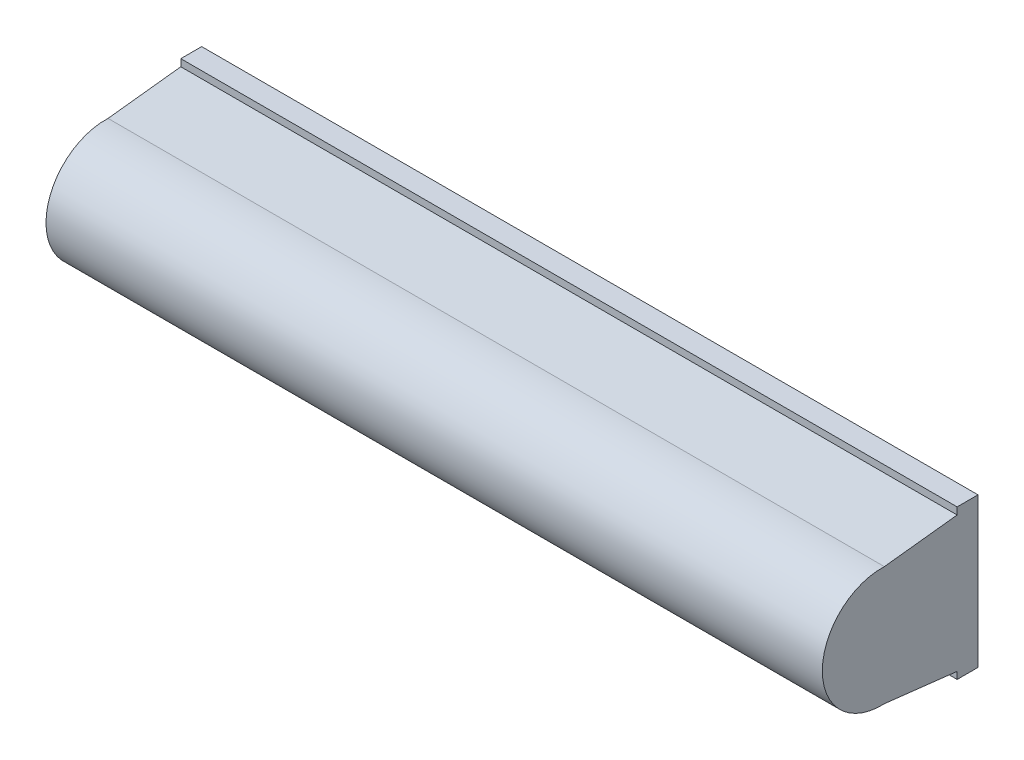
SolidWorks part; units mm, degrees
ref_plane "xy_plane" through (0, 0, 0) normal (0, 0, 1) x (1, 0, 0)
ref_plane "zx_plane" through (0, 0, 0) normal (0, 1, 0) x (1, 0, 0)
ref_plane "yz_plane" through (0, 0, 0) normal (1, 0, 0) x (0, 0, -1)
ref_axis "x_axis" through (-80.9, 0, 0) along (1, 0, 0)
ref_axis "y_axis" through (0, -50, 0) along (0, 1, 0)
ref_axis "z_axis" through (0, 0, -80.9) along (0, 0, 1)
sketch "Sketch1" plane through (0, 0, 0) normal (1, 0, 0) x (0, 0, -1)
  line L0 (0, -15.405) -> (0, 15.405)
  line L1 (0, 15.405) -> (-4.3, 15.405)
  line L2 (-4.3, 15.405) -> (-4.3, 13.955)
  line L3 (-4.3, 13.955) -> (-19.2957, 12.2383)
  line L4 (-19.2957, -12.2383) -> (-4.3, -13.955)
  line L5 (-4.3, -13.955) -> (-4.3, -15.405)
  line L6 (-4.3, -15.405) -> (0, -15.405)
  line L7 (80.9, 0) -> (-80.9, 0) construction
  line L8 (0, 50) -> (0, -50) construction
  line L9 (0, -50) -> (0, 50) construction
  arc A0 (-19.2957, 12.2383) -> (-19.2957, -12.2383) centre (-19.83, 0) ccw
  dimension "D1" = 12.25
  dimension "D2" = 32.08
  dimension "D3" = 4.3
  dimension "D4" = 1.45
  dimension "D5" = 30.81
  dimension "D6" = 185
extrude "Boss-Extrude1" add sketch "Sketch1" along normal mid plane 160
equation "\"D5@Sketch1\"=30.81mm 'measured specimen with calipers"
equation "\"D3@Sketch1\"=4.30mm  'measured specimen with calipers"
equation "\"D4@Sketch1\"=1.45mm  'measured specimen with calipers"
equation "\"D6@Sketch1\"=185deg 'eyeballed the specimen"
equation "\"D2@Sketch1\"=32.08mm  'measured specimen with calipers"
equation "\"D1@Sketch1\"=24.50mm/2  'measured specimen with calipers"
